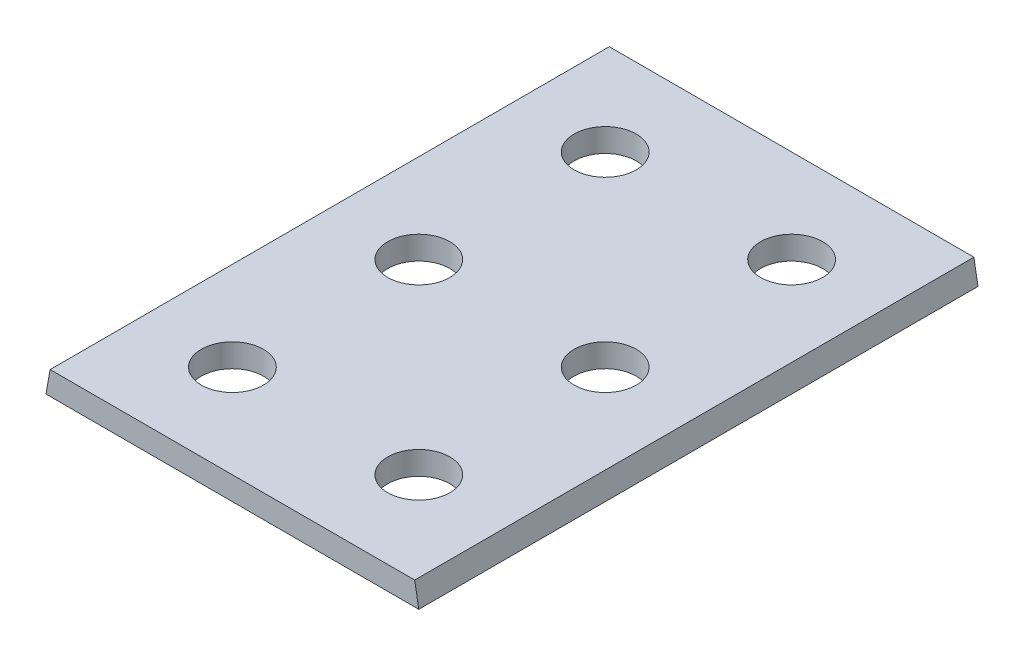
SolidWorks part; units mm, degrees
ref_plane "Front Plane" through (0, 0, 0) normal (0, 0, 1) x (1, 0, 0)
ref_plane "Top Plane" through (0, 0, 0) normal (0, 1, 0) x (1, 0, 0)
ref_plane "Right Plane" through (0, 0, 0) normal (1, 0, 0) x (0, 0, -1)
sketch "Sketch1" plane through (0, 0, 0) normal (0, 1, 0) x (1, 0, 0)
  line L1 (-45.4206, -63.5888) -> (-18.4206, -63.5888)
  line L2 (-45.4206, -63.5888) -> (-45.4206, -36.5888)
  line L3 (-45.4206, 98.4112) -> (62.5794, 98.4112)
  line L4 (62.5794, -63.5888) -> (62.5794, 98.4112)
  line L6 (-45.4206, 98.4112) -> (-45.4206, -36.5888)
  line L7 (-18.4206, -63.5888) -> (62.5794, -63.5888)
  circle A2 centre (-18.4206, -36.5888) radius 9
  circle A3 centre (35.5794, 71.4112) radius 9
  circle A4 centre (35.5794, 17.4112) radius 9
  circle A5 centre (-18.4206, 17.4112) radius 9
  circle A6 centre (-18.4206, 71.4112) radius 9
  circle A7 centre (35.5794, -36.5888) radius 9
  dimension "D1" = 108
  dimension "D2" = 162
extrude "Boss-Extrude1" add sketch "Sketch1" along normal blind 6.75
chamfer "Chamfer1" distance 6.75 angle 10 2 edges at (62.5794, 6.75, -17.4112) (-45.4206, 6.75, -17.4112) first distance on face at (62.5794, 3.375, -17.4112) first distance on face at (-45.4206, 3.375, -17.4112)
